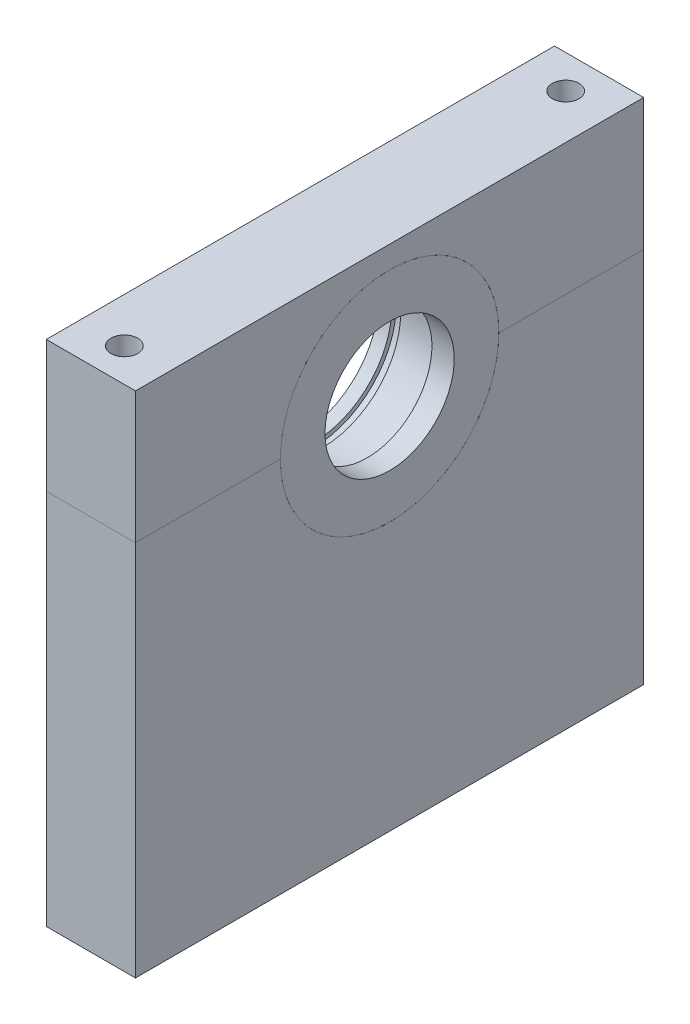
SolidWorks part; units mm, degrees
ref_plane "Front Plane" through (0, 0, 0) normal (0, 0, 1) x (1, 0, 0)
ref_plane "Top Plane" through (0, 0, 0) normal (0, 1, 0) x (1, 0, 0)
ref_plane "Right Plane" through (0, 0, 0) normal (1, 0, 0) x (0, 0, -1)
sketch "Sketch1" plane through (0, 0, 0) normal (0, 0, 1) x (1, 0, 0)
  line L0 (-44.079, 28.0482) -> (-34.079, 28.0482)
  line L1 (-34.079, 28.0482) -> (-34.079, 25.0482)
  line L2 (-34.079, 25.0482) -> (-29.079, 25.0482)
  line L3 (-29.079, 25.0482) -> (-29.079, 35.0482)
  line L4 (-29.079, 35.0482) -> (-49.079, 35.0482)
  line L5 (-49.079, 35.0482) -> (-49.079, 28.0482)
  line L6 (-49.079, 28.0482) -> (-46.079, 28.0482)
  line L7 (-46.079, 28.0482) -> (-46.079, 29.0482)
  line L8 (-46.079, 29.0482) -> (-44.079, 29.0482)
  line L9 (-44.079, 29.0482) -> (-44.079, 28.0482)
  line L10 (-85.0679, 10.5482) -> (6.0387, 10.5482) construction
  dimension "D1" = 24.5
  dimension "D2" = 20
  dimension "D3" = 17.5
  dimension "D4" = 2
  dimension "D5" = 10
  dimension "D6" = 3
  dimension "D7" = 1
  dimension "D8" = 3
revolve "Revolve1" add sketch "Sketch1" angle 360 about L10
sketch "Sketch2" plane through (-49.079, 0, 0) normal (-1, 0, 0) x (0, 0, 1)
  line L0 (-24.5, 10.5482) -> (-57, 10.5482)
  line L1 (-57, -18.9518) -> (57, -18.9518)
  line L2 (-57, -18.9518) -> (-57, 40.0482)
  line L3 (-57, 40.0482) -> (57, 40.0482)
  line L4 (57, -18.9518) -> (57, 40.0482)
  line L5 (0, 40.0482) -> (0, -18.9518) construction
  line L6 (-57, 10.5482) -> (57, 10.5482) construction
  line L7 (24.5, 10.5482) -> (57, 10.5482)
  line L8 (-34.5, 40.0482) -> (-34.5, -18.9518) construction
  line L9 (-29.5, 40.0482) -> (-29.5, -18.9518) construction
  line L10 (29.5, 40.0482) -> (29.5, -18.9518) construction
  line L11 (34.5, 40.0482) -> (34.5, -18.9518) construction
  circle A0 centre (0, 10.5482) radius 24.5 construction
  circle A1 centre (0, 10.5482) radius 24.5 construction
  point P0 (0, 10.5482)
  point P7 (0, 35.0482)
  point P9 (0, -13.9518)
  point P10 (24.5, 10.5482)
  point P11 (-24.5, 10.5482)
  circle M9 centre (0, 10.5482) radius 24.5
  dimension "D1" = 49
  dimension "D2" = 5
  dimension "D3" = 5
  dimension "D4" = 114
  dimension "D6" = 5
  dimension "D7" = 5
  dimension "D8" = 22.5
extrude "Boss-Extrude2" add sketch "Sketch2" against normal up to surface (20 mm away) separate body contours L7 L4 L3 L2 L0 M9 region at (-49.079, 11.7257, -40.75) up to face at (-29.079, 10.5482, 24.5)
extrude "Boss-Extrude3" add sketch "Sketch2<3>" against normal up to surface (20 mm away) separate body contours L7 L0 L2 L1 L4 M9 region at (-49.079, -15.1294, 0) up to face at (-29.079, 10.5482, 24.5)
sketch "Sketch2<3>" plane through (-49.079, 0, 0) normal (-1, 0, 0) x (0, 0, 1) same geometry as "Sketch2"
sketch "Sketch3" plane through (0, 40.0482, 0) normal (0, 1, 0) x (1, 0, 0)
  line L0 (-39.079, -57) -> (-39.079, 57) construction
  line L1 (-29.079, -57) -> (-49.079, -57) construction
  line L2 (-29.079, 57) -> (-49.079, 57) construction
  circle A0 centre (-39.079, 49.5) radius 3
  circle A1 centre (-39.079, -49.5) radius 3
  dimension "D1" = 7.5
  dimension "D3" = 6
  dimension "D4" = 6
  dimension "D2" = 7.5
extrude "Cut-Extrude1" cut sketch "Sketch3" against normal up to surface (59 mm away) up to face at (-39.079, -18.9518, 0)
sketch "Sketch4" plane through (0, -18.9518, 0) normal (0, -1, 0) x (1, 0, 0)
  line L0 (-29.079, 57) -> (-29.079, -57) construction
  line L1 (-49.079, 57) -> (-29.079, 57)
  line L2 (-49.079, 57) -> (-49.079, -57)
  line L3 (-49.079, -57) -> (-29.079, -57)
  line L4 (-29.079, 57) -> (-29.079, -57)
  circle A0 centre (-39.079, 49.5) radius 3
  circle A1 centre (-39.079, -49.5) radius 3
  dimension "D1" = 114
extrude "Boss-Extrude5" add sketch "Sketch4" along normal blind 55.05
